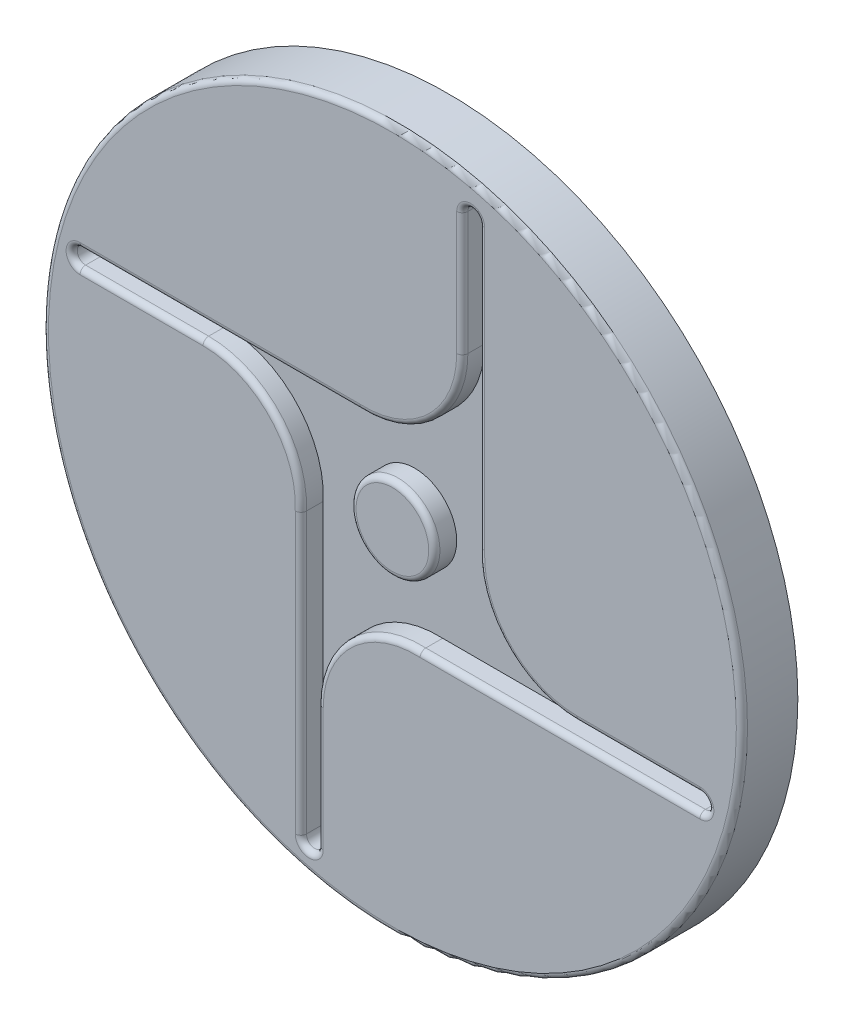
SolidWorks part; units mm, degrees
ref_plane "Front Plane" through (0, 0, 0) normal (0, 0, 1) x (1, 0, 0)
ref_plane "Top Plane" through (0, 0, 0) normal (0, 1, 0) x (1, 0, 0)
ref_plane "Right Plane" through (0, 0, 0) normal (1, 0, 0) x (0, 0, -1)
sketch "Sketch1" plane through (0, 0, 0) normal (0, 0, 1) x (1, 0, 0)
  circle A0 centre (0, 0) radius 62.5
  dimension "D1" = 125
extrude "Boss-Extrude1" add sketch "Sketch1" along normal blind 10 contours A0
sketch "Sketch3" plane through (0, 0, 10) normal (0, 0, 1) x (1, 0, 0)
  line L0 (15.5, 5) -> (15.5, 55)
  line L1 (12.5, 55) -> (12.5, 33)
  line L2 (4.9794, -16.3488) -> (54.9794, -16.3488)
  line L3 (54.9794, -13.3488) -> (32.9794, -13.3488)
  line L4 (-16.3694, -5.8282) -> (-16.3694, -55.8282)
  line L5 (-13.3694, -55.8282) -> (-13.3694, -33.8282)
  line L6 (-5.8488, 15.5206) -> (-55.8488, 15.5206)
  line L7 (-55.8488, 12.5206) -> (-33.8488, 12.5206)
  arc A0 (15.5, 55) -> (12.5, 55) centre (14, 55) ccw
  arc A1 (12.5, 33) -> (-5.8488, 15.5206) centre (-5, 33) cw
  arc A2 (32.9794, -13.3488) -> (15.5, 5) centre (32.9794, 4.1512) cw
  arc A3 (54.9794, -16.3488) -> (54.9794, -13.3488) centre (54.9794, -14.8488) ccw
  arc A4 (-13.3694, -33.8282) -> (4.9794, -16.3488) centre (4.1306, -33.8282) cw
  arc A5 (-16.3694, -55.8282) -> (-13.3694, -55.8282) centre (-14.8694, -55.8282) ccw
  arc A6 (-33.8488, 12.5206) -> (-16.3694, -5.8282) centre (-33.8488, -4.9794) cw
  arc A7 (-55.8488, 15.5206) -> (-55.8488, 12.5206) centre (-55.8488, 14.0206) ccw
  circle A8 centre (0, 0) radius 7.5
  circle A9 centre (0, 0) radius 62.5 construction
  point P32 (-0.4347, -0.4141)
  point P34 (0, 0)
  dimension "D7" = 17.5
  dimension "D9" = 15
  dimension "D1" = 5
  dimension "D2" = 15.5
  dimension "D3" = 55
  dimension "D4" = 3
  dimension "D5" = 22
  dimension "D6" = 5
  dimension "D8" = 4
extrude "Cut-Extrude1" cut sketch "Sketch3" against normal blind 4
fillet "Fillet1" radius 1 2 edges at (62.5, 0, 10) (7.5, 0, 10)
fillet "Fillet4" radius 1 16 edges at (-16.3694, -30.8282, 10) (-14.8694, -57.3282, 10) (-13.3694, -44.8282, 10) (56.4794, -14.8488, 10) (43.9794, -13.3488, 10) (14, 56.5, 10) (-57.3488, 14.0206, 10) (-44.8488, 12.5206, 10) (-7.9399, -21.1573, 10) (29.9794, -16.3488, 10) (20.3085, -7.9193, 10) (15.5, 30, 10) (12.5, 44, 10) (7.0705, 20.3291, 10) (-30.8488, 15.5206, 10) (-21.1779, 7.0911, 10)
sketch "Sketch4" plane through (0, 0, 0) normal (0, 0, -1) x (-1, 0, 0)
  circle A0 centre (0, 0) radius 7.5
  dimension "D1" = 15
extrude "Boss-Extrude2" add sketch "Sketch4" along normal blind 25
